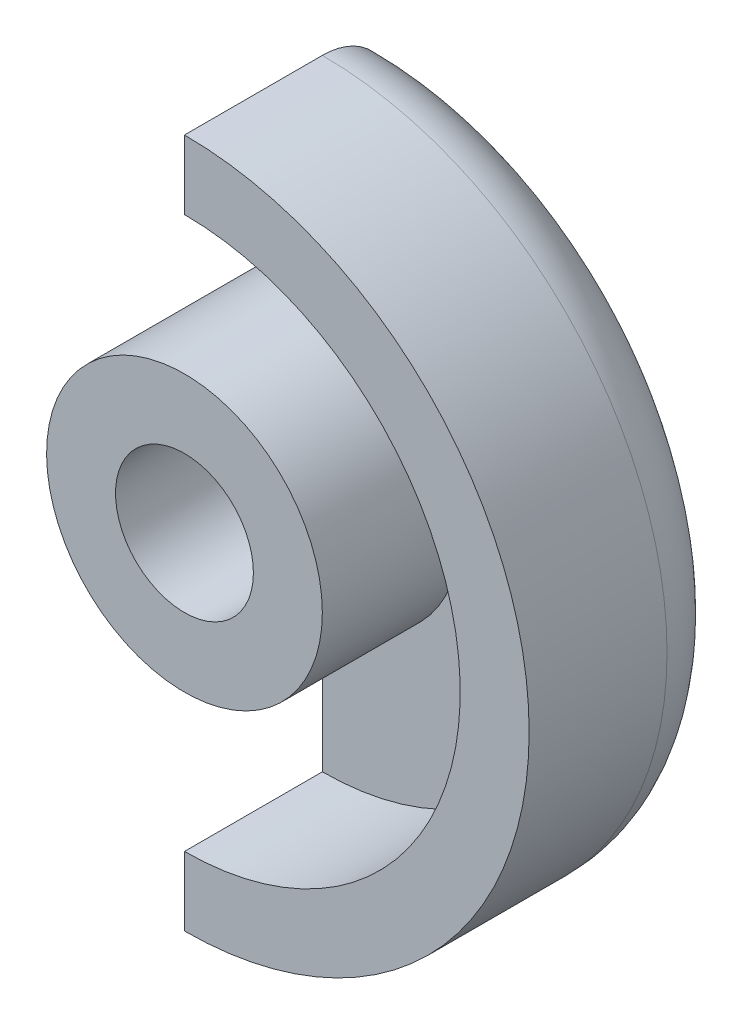
SolidWorks part; units mm, degrees
ref_plane "Front Plane" through (0, 0, 0) normal (0, 0, 1) x (1, 0, 0)
ref_plane "Top Plane" through (0, 0, 0) normal (0, 1, 0) x (1, 0, 0)
ref_plane "Right Plane" through (0, 0, 0) normal (1, 0, 0) x (0, 0, -1)
sketch "Sketch1" plane through (0, 0, 0) normal (0, 0, 1) x (1, 0, 0)
  circle A0 centre (0, 0) radius 1
  circle A1 centre (0, 0) radius 2
extrude "Boss-Extrude1" add sketch "Sketch1" along normal blind 2
sketch "Sketch2" plane through (0, 0, 0) normal (0, 0, 1) x (1, 0, 0)
  line L0 (0, 5) -> (0, 4)
  line L1 (0, -4) -> (0, -5)
  arc A0 (0, -4) -> (0, 4) centre (0, 0) ccw
  arc A1 (0, -5) -> (0, 5) centre (0, 0) ccw
extrude "Boss-Extrude2" add sketch "Sketch2" along normal blind 2 separate body
sketch "Sketch3" plane through (0, 0, 2) normal (0, 0, 1) x (1, 0, 0)
  line L0 (0, 5) -> (0, 1)
  line L1 (0, -1) -> (0, -5)
  arc A0 (0, -5) -> (0, 5) centre (0, 0) ccw
  arc A1 (0, -1) -> (0, 1) centre (0, 0) ccw
sketch "Sketch4" plane through (0, 0, 2) normal (0, 0, 1) x (1, 0, 0)
  circle A0 centre (0, 0) radius 1
  circle A1 centre (0, 0) radius 5
sketch "Sketch5" plane through (0, 0, 0) normal (0, 0, 1) x (1, 0, 0)
  line L0 (0, 5) -> (0, 2)
  line L1 (0, -2) -> (0, -5)
  arc A3 (0, -5) -> (0, 5) centre (0, 0) ccw
  arc A4 (0, 2) -> (0, -2) centre (0, 0) ccw
  circle A5 centre (0, 0) radius 1
extrude "Boss-Extrude3" add sketch "Sketch5" against normal blind 1
chamfer "Chamfer1" distance 1 angle 45 1 edges at (1, 0, -1)
fillet "Fillet1" radius 1 3 edges at (5, 0, -1) (0, -2, -0.5) (0, 2, -0.5)
